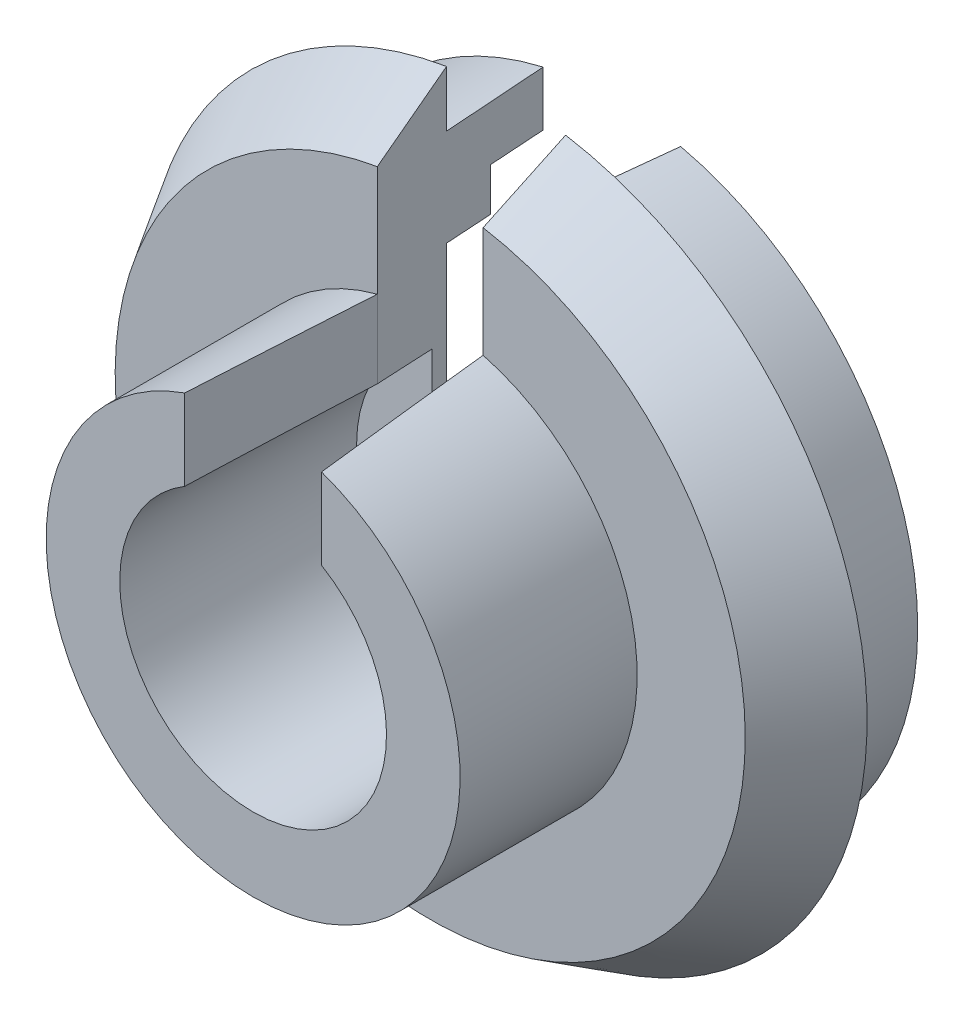
SolidWorks part; units mm, degrees
material "ABS"
ref_plane "Спереди" through (0, 0, 0) normal (0, 0, 1) x (1, 0, 0)
ref_plane "Сверху" through (0, 0, 0) normal (0, 1, 0) x (1, 0, 0)
ref_plane "Справа" through (0, 0, 0) normal (1, 0, 0) x (0, 0, -1)
sketch "Эскиз1" plane through (0, 0, 0) normal (0, 1, 0) x (1, 0, 0)
  line L0 (6.85, 0) -> (7.85, 1.65)
  line L1 (2.9, -3.85) -> (2.9, 1.3)
  line L2 (0, 0) -> (0, -3.85)
  line L3 (0, -3.85) -> (4.5, -3.85)
  line L4 (4.5, 0) -> (4.5, -3.85)
  line L5 (4.5, 0) -> (6.85, 0)
  line L6 (0, 0) -> (0, 1.65)
  line L7 (4.6, 1.65) -> (7.85, 1.65)
  line L8 (5.5, 3.95) -> (5.5, 2.7)
  line L9 (4.6, 1.65) -> (6.65, 1.65)
  line L10 (0, 1.65) -> (0, 3.95)
  line L11 (0, 3.95) -> (6.65, 3.95)
  line L12 (6.65, 1.65) -> (6.65, 3.95)
  line L13 (5.5, 2.7) -> (4.6, 2.7)
  line L14 (4.6, 2.7) -> (4.6, 1.65)
  line L15 (2.9, 1.3) -> (0, 1.3)
  line L16 (0, 1.3) -> (0, 1.65)
  line L17 (4.6, 1.65) -> (-0.0789, 1.65)
  dimension "D1" = 7.8
  dimension "D2" = 3.85
  dimension "D3" = 2.3
  dimension "D4" = 4.5
  dimension "D5" = 7.85
  dimension "D6" = 6.65
  dimension "D7" = 1.25
  dimension "D8" = 5.5
  dimension "D9" = 4.6
  dimension "D10" = 5.15
  dimension "D11" = 2.9
  dimension "D12" = 6.85
revolve "Повернуть1" add sketch "Эскиз1" angle 360 about L2
sketch "Эскиз2" plane through (0, 0, 0) normal (0, 0, 1) x (1, 0, 0)
  line L0 (0, 0) -> (0, 10.1342) construction
  line L1 (-1.15, 0) -> (-1.15, 10.5074)
  line L2 (-1.15, 10.5074) -> (1.15, 10.5074)
  line L3 (1.15, 10.5074) -> (1.15, 0)
  line L4 (1.15, 0) -> (-1.15, 0)
  circle A0 centre (0, 0) radius 1.5
  dimension "D1" = 3
  dimension "D2" = 2.3
extrude "Вырез-Вытянуть1" cut sketch "Эскиз2" against normal blind 10 draft 5 and the other way blind 10 draft 5
